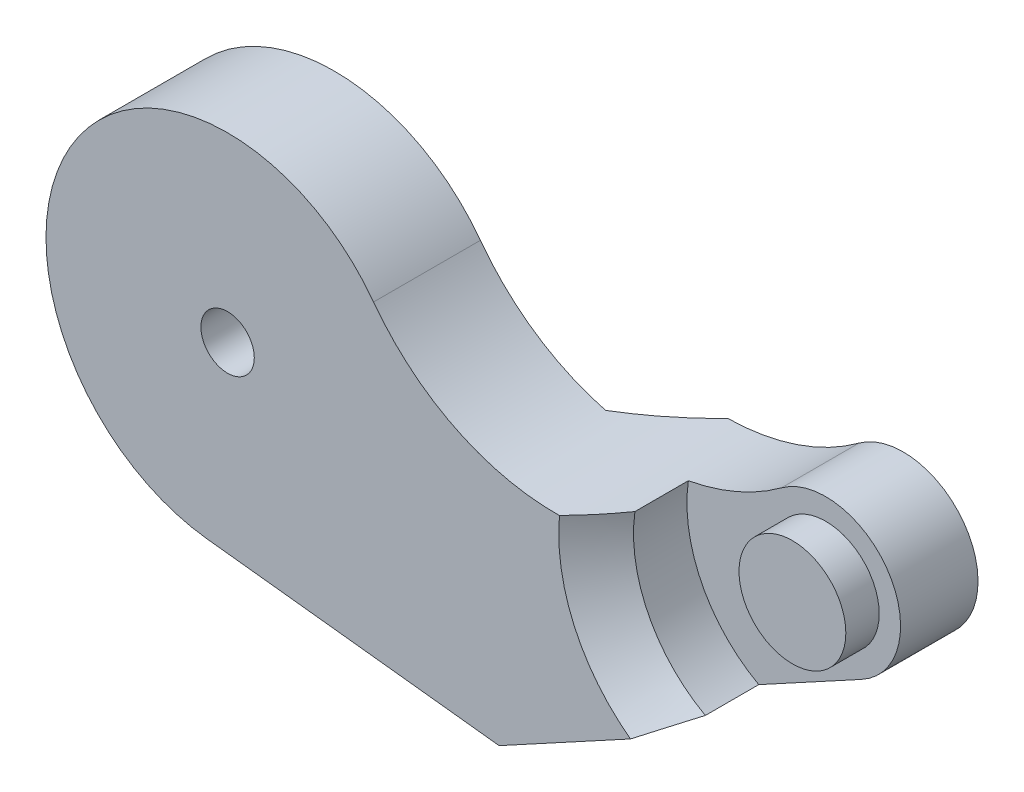
SolidWorks part; units mm, degrees
ref_plane "Front Plane" through (0, 0, 0) normal (0, 0, 1) x (1, 0, 0)
ref_plane "Top Plane" through (0, 0, 0) normal (0, 1, 0) x (1, 0, 0)
ref_plane "Right Plane" through (0, 0, 0) normal (1, 0, 0) x (0, 0, -1)
sketch "Sketch1" plane through (0, 0, 0) normal (0, 0, 1) x (1, 0, 0)
  line L0 (0, 0) -> (190, 0) construction
  line L1 (-7.6429, -67.5691) -> (101.66, -79.9327)
  line L2 (203.3804, -24.596) -> (101.66, -79.9327)
  arc A0 (54.6667, 40.442) -> (-7.6429, -67.5691) centre (0, 0) ccw
  arc A1 (203.3804, -24.596) -> (173.3982, 22.5473) centre (190, 0) ccw
  arc A2 (54.6667, 40.442) -> (173.3982, 22.5473) centre (123, 90.9945) ccw
  dimension "D1" = 136
  dimension "D2" = 56
  dimension "D3" = 190
  dimension "D4" = 85
  dimension "D5" = 145
  dimension "D6" = 110
extrude "Boss-Extrude7" add sketch "Sketch1" against normal blind 40 contours L2 L1 A0 A2 A1
sketch "Sketch7" plane through (0, 0, 0) normal (0, 0, 1) x (1, 0, 0)
  circle A0 centre (190, 0) radius 52
extrude "Cut-Extrude1" cut sketch "Sketch7" against normal blind 34
sketch "Sketch11" plane through (0, 0, -34) normal (0, 0, 1) x (1, 0, 0)
  circle A0 centre (190, 0) radius 20
extrude "Boss-Extrude8" add sketch "Sketch11" along normal blind 12.5 contours A0
chamfer "Chamfer1" distance 14 angle 45 1 edges at (143.4463, -23.1679, 0)
sketch "Sketch14" plane through (0, 0, -40) normal (0, 0, -1) x (-1, 0, 0)
  line L5 (-91.66, -78.8016) -> (-101.5624, 8.7423)
  line L10 (-203.3804, -24.596) -> (-101.66, -79.9327)
  line L11 (-101.66, -79.9327) -> (7.6429, -67.5691)
  line L12 (-203.3804, -24.596) -> (-101.66, -79.9327)
  line L13 (-101.66, -79.9327) -> (-91.66, -78.8016)
  arc A5 (-173.3982, 22.5473) -> (-203.3804, -24.596) centre (-190, 0) ccw
  arc A6 (7.6429, -67.5691) -> (-54.6667, 40.442) centre (0, 0) ccw
  arc A10 (-173.3982, 22.5473) -> (-54.6667, 40.442) centre (-123, 90.9945) ccw
  arc A11 (-173.3982, 22.5473) -> (-203.3804, -24.596) centre (-190, 0) ccw
  arc A13 (-173.3982, 22.5473) -> (-101.5624, 8.7423) centre (-123, 90.9945) ccw
  point P2 (-101.6247, -79.9327)
  dimension "D1" = 0
  dimension "D2" = 10
extrude "Boss-Extrude10" add sketch "Sketch14" along normal blind 29 from surface starting at face at (210, 0, -34)
chamfer "Chamfer5" distance 23 angle 45 1 edges at (96.6112, -35.0296, -63)
sketch "Sketch16" plane through (0, 0, 0) normal (0, 0, 1) x (1, 0, 0)
  circle A0 centre (0, 0) radius 10
extrude "Cut-Extrude2" cut sketch "Sketch16" against normal blind 122 contours A0
